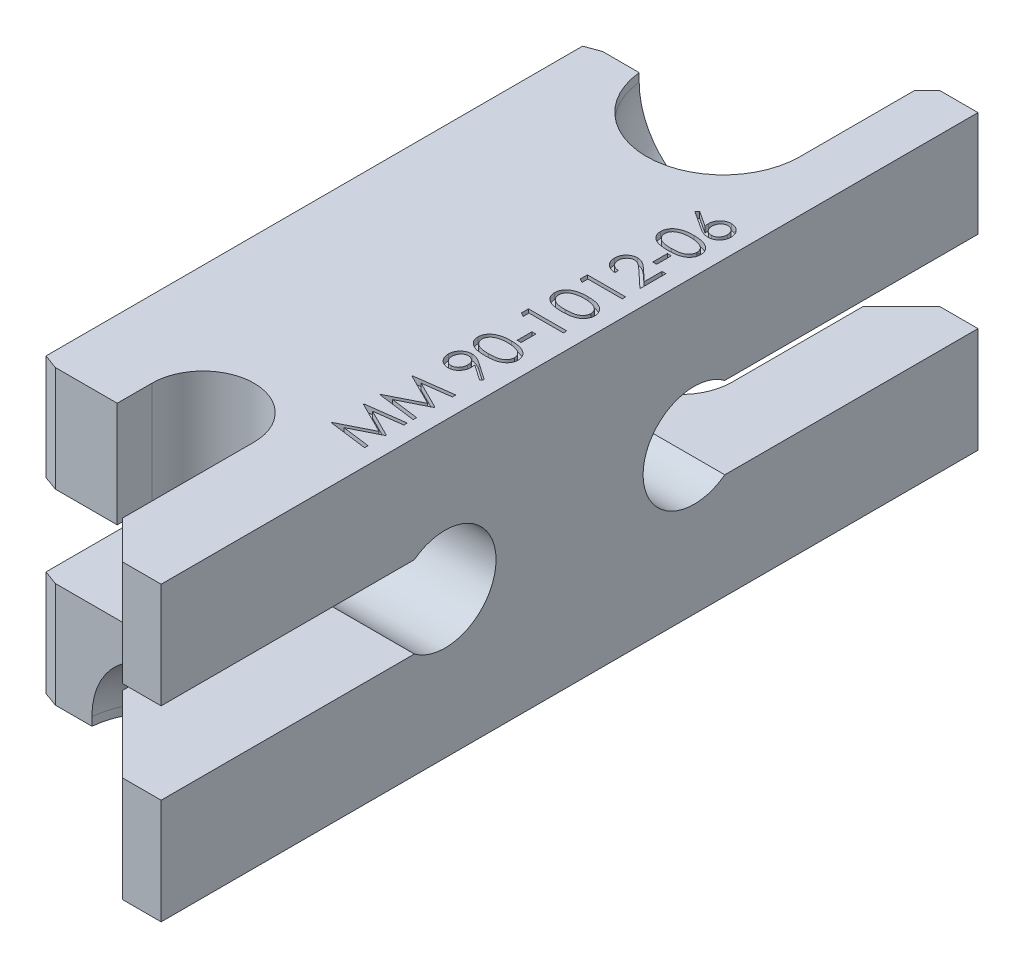
SolidWorks part; units mm, degrees
material "Acero M2"
ref_plane "Alzado" through (0, 0, 0) normal (0, 0, 1) x (1, 0, 0)
ref_plane "Planta" through (0, 0, 0) normal (0, 1, 0) x (1, 0, 0)
ref_plane "Vista lateral" through (0, 0, 0) normal (1, 0, 0) x (0, 0, -1)
sketch "Croquis1" plane through (0, 0, 0) normal (0, 1, 0) x (1, 0, 0)
  line L1 (15.875, -50.8) -> (0, -50.8)
  line L2 (15.875, -50.8) -> (15.875, 0)
  line L3 (15.875, 0) -> (0, 0)
  line L4 (0, -50.8) -> (0, 0)
  line L5 (7.9375, 0) -> (7.9375, -50.8) construction
  line L6 (15.875, -25.4) -> (0, -25.4) construction
  point P380 (7.9375, -25.4)
  dimension "D1" = 15.875
  dimension "D2" = 50.8
extrude "Saliente-Extruir1" add sketch "Croquis1" along normal blind 18.1864
sketch "Croquis2" plane through (15.875, 0, 0) normal (1, 0, 0) x (0, 0, -1)
  line L0 (-50.8, 9.0932) -> (-33.147, 9.0932) construction
  line L1 (-50.8, 18.1864) -> (-50.8, 0) construction
  line L2 (-33.147, 9.0932) -> (-17.653, 9.0932) construction
  circle A0 centre (-33.147, 9.0932) radius 3.175
  circle A1 centre (-17.653, 9.0932) radius 3.175
  dimension "D1" = 6.35
  dimension "D2" = 33.147
  dimension "D3" = 15.494
extrude "Cortar-Extruir1" cut sketch "Croquis2" against normal through all
sketch "Croquis3" plane through (15.875, 0, 0) normal (1, 0, 0) x (0, 0, -1)
  line L0 (-33.147, 9.0932) -> (-50.8, 9.0932) construction
  line L1 (-50.8, 18.1864) -> (-50.8, 0) construction
  line L2 (-33.147, 6.5532) -> (-50.8, 6.5532)
  line L3 (-33.147, 11.6332) -> (-50.8, 11.6332)
  line L4 (-17.653, 9.0932) -> (0, 9.0932) construction
  line L5 (0, 18.1864) -> (0, 0) construction
  line L6 (-17.653, 11.6332) -> (0, 11.6332)
  line L7 (-17.653, 6.5532) -> (0, 6.5532)
  arc A0 (-33.147, 6.5532) -> (-33.147, 11.6332) centre (-33.147, 9.0932) ccw
  arc A1 (-50.8, 11.6332) -> (-50.8, 6.5532) centre (-50.8, 9.0932) ccw
  arc A2 (-17.653, 11.6332) -> (-17.653, 6.5532) centre (-17.653, 9.0932) ccw
  arc A3 (0, 6.5532) -> (0, 11.6332) centre (0, 9.0932) ccw
  point P5 (-41.9735, 9.0932)
  point P10 (-8.8265, 9.0932)
  dimension "D1" = 5.08
extrude "Cortar-Extruir2" cut sketch "Croquis3" against normal through all
sketch "Croquis4" plane through (0, 0, 0) normal (0, -1, 0) x (1, 0, 0)
  line L0 (15.875, 50.8) -> (15.875, 0) construction
  line L1 (0, 50.8) -> (8.763, 50.8)
  line L2 (0, 50.8) -> (0, 42.418)
  line L3 (0, 42.418) -> (8.763, 42.418)
  line L4 (8.763, 50.8) -> (8.763, 42.418)
  line L5 (4.3815, 42.418) -> (4.3815, 50.8) construction
  line L6 (0, 46.609) -> (8.763, 46.609) construction
  line L7 (0, 0) -> (8.763, 0)
  line L8 (0, 0) -> (0, 8.382)
  line L9 (0, 8.382) -> (8.763, 8.382)
  line L10 (8.763, 0) -> (8.763, 8.382)
  line L11 (4.3815, 8.382) -> (4.3815, 0) construction
  line L12 (0, 4.191) -> (8.763, 4.191) construction
  point P124 (4.3815, 4.191)
  point P164 (4.3815, 46.609)
  dimension "D1" = 34.036
  dimension "D2" = 7.112
extrude "Cortar-Extruir3" cut sketch "Croquis4" against normal through all
sketch "Croquis5" plane through (0, 0, 0) normal (0, -1, 0) x (1, 0, 0)
  line L0 (8.763, 50.8) -> (13.4874, 50.8)
  line L1 (8.763, 50.8) -> (15.875, 50.8) construction
  line L2 (13.4874, 50.8) -> (8.763, 46.0756)
  line L3 (8.763, 42.418) -> (8.763, 50.8) construction
  line L4 (8.763, 46.0756) -> (8.763, 50.8)
  line L5 (15.875, 50.8) -> (15.875, 0) construction
  line L6 (0, 25.4) -> (15.875, 25.4) construction
  line L7 (0, 8.382) -> (0, 42.418) construction
  line L8 (8.763, 4.7244) -> (8.763, 0)
  line L9 (13.4874, 0) -> (8.763, 4.7244)
  line L10 (8.763, 0) -> (13.4874, 0)
  dimension "D1" = 45
  dimension "D2" = 2.3876
extrude "Cortar-Extruir4" cut sketch "Croquis5" against normal through all
chamfer "Chaflán1" distance 0.9144 angle 20 4 edges at (0, 14.9098, 8.382) (0, 3.2766, 8.382) (0, 14.9098, 42.418) (0, 3.2766, 42.418) first distance on face at (4.3815, 14.9098, 8.382) first distance on face at (4.3815, 3.2766, 8.382) first distance on face at (4.3815, 14.9098, 42.418) first distance on face at (4.3815, 3.2766, 42.418)
sketch "Croquis6" plane through (0, 0, 0) normal (0, -1, 0) x (1, 0, 0)
  line L0 (7.9375, 50.8) -> (7.9375, 42.9006) construction
  line L1 (12.7127, 50.8) -> (12.7127, 42.9006)
  line L2 (3.1623, 50.8) -> (3.1623, 42.9006)
  line L3 (0, 25.4) -> (15.875, 25.4) construction
  line L4 (0, 8.7148) -> (0, 42.0852) construction
  line L5 (15.875, 50.8) -> (15.875, 0) construction
  line L6 (7.9375, 25.4) -> (7.9375, 42.9006) construction
  line L7 (13.4874, 50.8) -> (15.875, 50.8) construction
  arc A0 (12.7127, 50.8) -> (3.1623, 50.8) centre (7.9375, 50.8) ccw
  arc A1 (3.1623, 42.9006) -> (12.7127, 42.9006) centre (7.9375, 42.9006) ccw
  point P2 (7.9375, 46.8503)
  dimension "D1" = 9.5504
  dimension "D2" = 7.8994
extrude "Cortar-Extruir5" cut sketch "Croquis6" against normal offset from surface (5.2832 mm away) 1.27 up to face at (7.9597, 6.5532, 43.0876)
sketch "Croquis7" plane through (0, 18.1864, 0) normal (0, 1, 0) x (1, 0, 0)
  line L0 (0, -25.4) -> (15.875, -25.4) construction
  line L1 (0, -25.4) -> (15.875, -25.4) construction
  line L2 (12.7127, -50.8) -> (12.7127, -42.9006)
  line L3 (3.1623, -42.9006) -> (3.1623, -50.8)
  line L4 (12.7127, -50.8) -> (12.7127, -42.9006) construction
  line L5 (3.1623, -42.9006) -> (3.1623, -50.8) construction
  line L6 (3.1623, -7.8994) -> (3.1623, 0)
  line L7 (12.7127, 0) -> (12.7127, -7.8994)
  arc A0 (3.1623, 0) -> (12.7127, 0) centre (7.9375, 0) cw
  arc A1 (12.7127, -7.8994) -> (3.1623, -7.8994) centre (7.9375, -7.8994) cw
  arc A2 (12.7127, -42.9006) -> (3.1623, -42.9006) centre (7.9375, -42.9006) ccw
  arc A3 (3.1623, -50.8) -> (12.7127, -50.8) centre (7.9375, -50.8) ccw
  arc A4 (12.7127, -42.9006) -> (3.1623, -42.9006) centre (7.9375, -42.9006) ccw construction
  arc A5 (3.1623, -50.8) -> (12.7127, -50.8) centre (7.9375, -50.8) ccw construction
  dimension "D1" = 0
extrude "Cortar-Extruir6" cut sketch "Croquis7" against normal offset from surface (5.2832 mm away) 1.27 up to face at (7.9597, 11.6332, 7.7124)
fillet "Redondeo1" radius 4.7625 4 edges at (12.7127, 5.2832, 46.463) (8.1791, 12.9032, 12.6685) (8.1791, 5.2832, 38.1315) (12.7127, 12.9032, 4.337)
sketch "Croquis8" plane through (0, 0, 0) normal (0, -1, 0) x (1, 0, 0)
  line L0 (7.9375, 50.8) -> (7.9375, 41.9608) construction
  line L1 (8.763, 50.8) -> (8.763, 41.9608)
  line L2 (7.112, 50.8) -> (7.112, 41.9608)
  line L3 (7.9375, 50.8) -> (7.9375, 42.9006) construction
  line L4 (8.763, 42.9006) -> (8.763, 46.0756) construction
  line L5 (13.4874, 50.8) -> (15.875, 50.8) construction
  line L6 (0, 25.4) -> (15.875, 25.4) construction
  line L7 (0, 25.4) -> (15.875, 25.4) construction
  line L8 (7.9375, 0) -> (7.9375, 8.8392) construction
  line L9 (8.763, 0) -> (8.763, 8.8392)
  line L10 (7.112, 0) -> (7.112, 8.8392)
  arc A0 (8.763, 50.8) -> (7.112, 50.8) centre (7.9375, 50.8) ccw
  arc A1 (7.112, 41.9608) -> (8.763, 41.9608) centre (7.9375, 41.9608) ccw
  arc A2 (8.763, 0) -> (7.112, 0) centre (7.9375, 0) cw
  arc A3 (7.112, 8.8392) -> (8.763, 8.8392) centre (7.9375, 8.8392) cw
  point P2 (7.9375, 46.3804)
  point P19 (7.9375, 4.4196)
  dimension "D1" = 8.8392
extrude "Cortar-Extruir7" cut sketch "Croquis8" against normal through all
sketch "Croquis9" plane through (0, 0, 0) normal (0, -1, 0) x (1, 0, 0)
  line L0 (7.9375, 0) -> (7.9375, 10.541) construction
  line L1 (4.7625, 0) -> (4.7625, 10.541)
  line L2 (11.1125, 0) -> (11.1125, 10.541)
  line L3 (7.9375, 25.4) -> (7.9375, 42.9006) construction
  line L4 (15.875, 0) -> (13.4874, 0) construction
  arc A0 (4.7625, 0) -> (11.1125, 0) centre (7.9375, 0) ccw
  arc A1 (11.1125, 10.541) -> (4.7625, 10.541) centre (7.9375, 10.541) ccw
  point P2 (7.9375, 5.2705)
  dimension "D1" = 6.35
  dimension "D2" = 10.541
extrude "Cortar-Extruir8" cut sketch "Croquis9" against normal up to surface (6.5532 mm away) up to face at (7.7902, 6.5532, 8.0203)
sketch "Croquis10" plane through (0, 18.1864, 0) normal (0, 1, 0) x (1, 0, 0)
  line L0 (0, -25.4) -> (15.875, -25.4) construction
  line L1 (0, -25.4) -> (15.875, -25.4) construction
  line L2 (4.7625, 0) -> (4.7625, -10.541)
  line L3 (11.1125, -10.541) -> (11.1125, 0)
  line L4 (4.7625, 0) -> (4.7625, -10.541) construction
  line L5 (11.1125, -10.541) -> (11.1125, 0) construction
  line L6 (11.1125, -40.259) -> (11.1125, -50.8)
  line L7 (4.7625, -50.8) -> (4.7625, -40.259)
  arc A0 (11.1125, -50.8) -> (4.7625, -50.8) centre (7.9375, -50.8) cw
  arc A1 (4.7625, -40.259) -> (11.1125, -40.259) centre (7.9375, -40.259) cw
  arc A2 (4.7625, -10.541) -> (11.1125, -10.541) centre (7.9375, -10.541) ccw
  arc A3 (11.1125, 0) -> (4.7625, 0) centre (7.9375, 0) ccw
  arc A4 (4.7625, -10.541) -> (11.1125, -10.541) centre (7.9375, -10.541) ccw construction
  arc A5 (11.1125, 0) -> (4.7625, 0) centre (7.9375, 0) ccw construction
  dimension "D1" = 0
extrude "Cortar-Extruir9" cut sketch "Croquis10" against normal up to surface (6.5532 mm away) up to face at (7.7902, 11.6332, 42.7797)
sketch "Croquis11" plane through (0, 18.1864, 0) normal (0, 1, 0) x (1, 0, 0)
  line L0 (14.8472, -43.4561) -> (14.8472, -7.3439) construction
  line L1 (0, -25.4) -> (15.875, -25.4) construction
  text T0 "MM 90-1012-06" font "Century Gothic" height 2.3813
  point P4 (14.8472, -25.4)
extrude "Cortar-Extruir10" cut sketch "Croquis11" against normal blind 0.381
